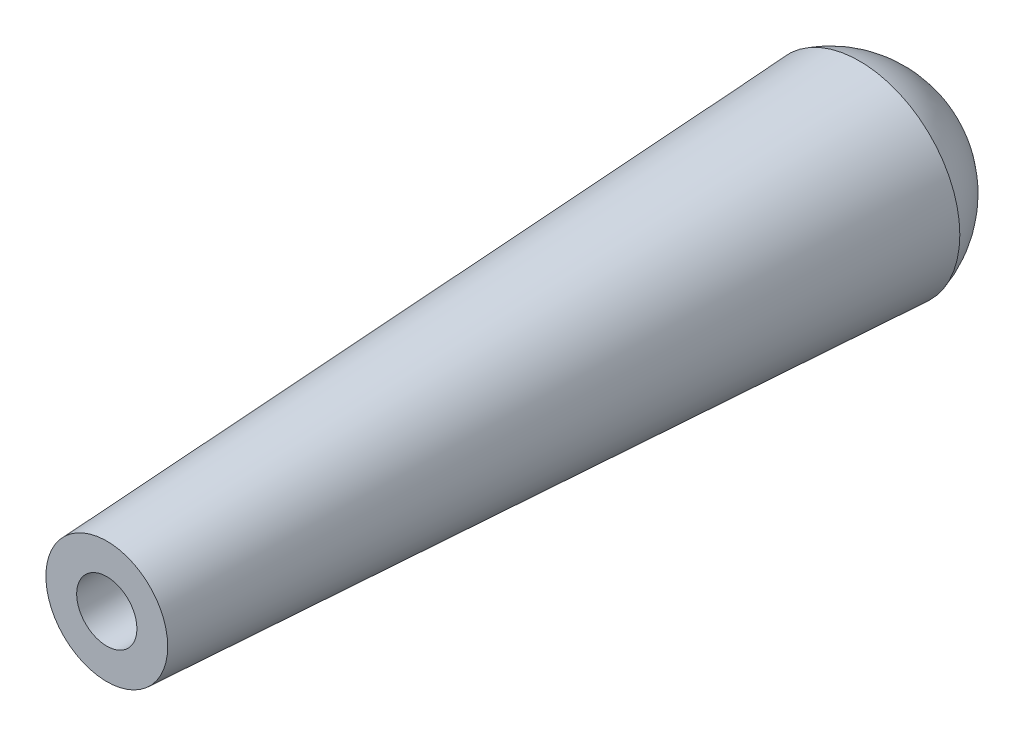
SolidWorks part; units mm, degrees
ref_plane "Front Plane" through (0, 0, 0) normal (0, 0, 1) x (1, 0, 0)
ref_plane "Top Plane" through (0, 0, 0) normal (0, 1, 0) x (1, 0, 0)
ref_plane "Right Plane" through (0, 0, 0) normal (1, 0, 0) x (0, 0, -1)
sketch "Sketch1" plane through (0, 0, 0) normal (0, 0, 1) x (1, 0, 0)
  circle A0 centre (0, 0) radius 50.8
extrude "Boss-Extrude1" add sketch "Sketch1" along normal blind 381 draft 3
dome "Dome1" faces to dome 1 distance 38.1 reverse direction no elliptical dome no face at (50.8, 0, 0) parameters "D1"=38.1
sketch "Sketch5" plane through (0, 0, 381) normal (0, 0, 1) x (1, 0, 0)
  circle A0 centre (0, 0) radius 15.24
extrude "Cut-Extrude1" cut sketch "Sketch5" against normal blind 254
